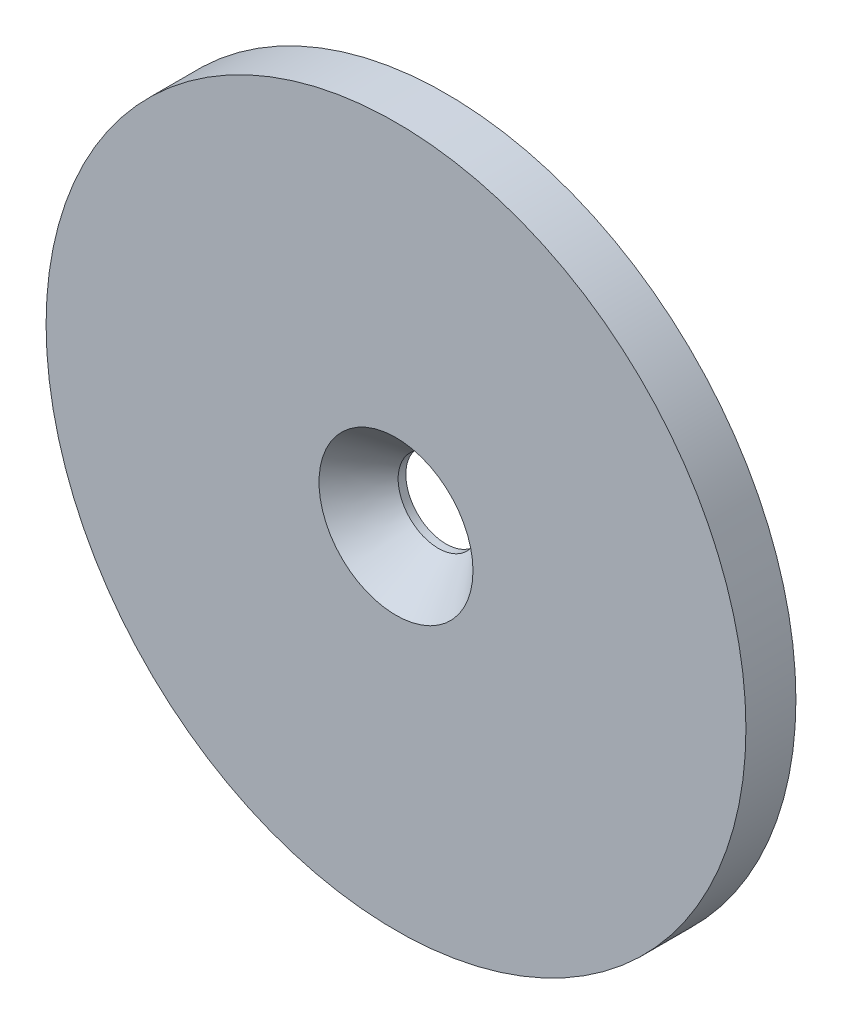
SolidWorks part; units mm, degrees
ref_plane "Front Plane" through (0, 0, 0) normal (0, 0, 1) x (1, 0, 0)
ref_plane "Top Plane" through (0, 0, 0) normal (0, 1, 0) x (1, 0, 0)
ref_plane "Right Plane" through (0, 0, 0) normal (1, 0, 0) x (0, 0, -1)
sketch "Sketch1" plane through (0, 0, 0) normal (0, 0, 1) x (1, 0, 0)
  circle A0 centre (0, 0) radius 22.225
  circle A1 centre (0, 0) radius 2.4892
  dimension "D1" = 44.45
  dimension "D2" = 4.9784
extrude "Boss-Extrude1" add sketch "Sketch1" along normal blind 3.175
hole_wizard "CSK for #10 Flat Head Machine Screw1" positions "3DSketch1" profile "Sketch2" countersink size "#10" standard "ANSI Inch" end condition through all
sketch3d "3DSketch1"
  line L0 (0, 0, 3.175) -> (0, 0, 0) construction
  point P0 (0, 0, 3.175)
  point P3 (0, 0, 3.175)
sketch "Sketch2" plane through (0, 0, 3.175) normal (1, 0, 0) x (0, -1, 0)
  line L0 (0, 0) -> (0, 3.175)
  line L1 (0, 3.175) -> (2.5527, 3.175)
  line L2 (2.5527, 3.175) -> (2.5527, 2.6882)
  line L3 (2.5527, 2.6882) -> (4.8895, 0)
  line L5 (4.8895, 0) -> (0, 0)
  line L6 (-2.5527, 2.6882) -> (-4.8895, 0) construction
  line L11 (0, -6.35) -> (0, 107.95) construction
  dimension "Thru Hole Dia." = 5.1054
  dimension "Thru Hole Depth" = 3.175
  dimension "Near C'Sink Dia." = 9.779
  dimension "Near C'Sink Angle" = 82
